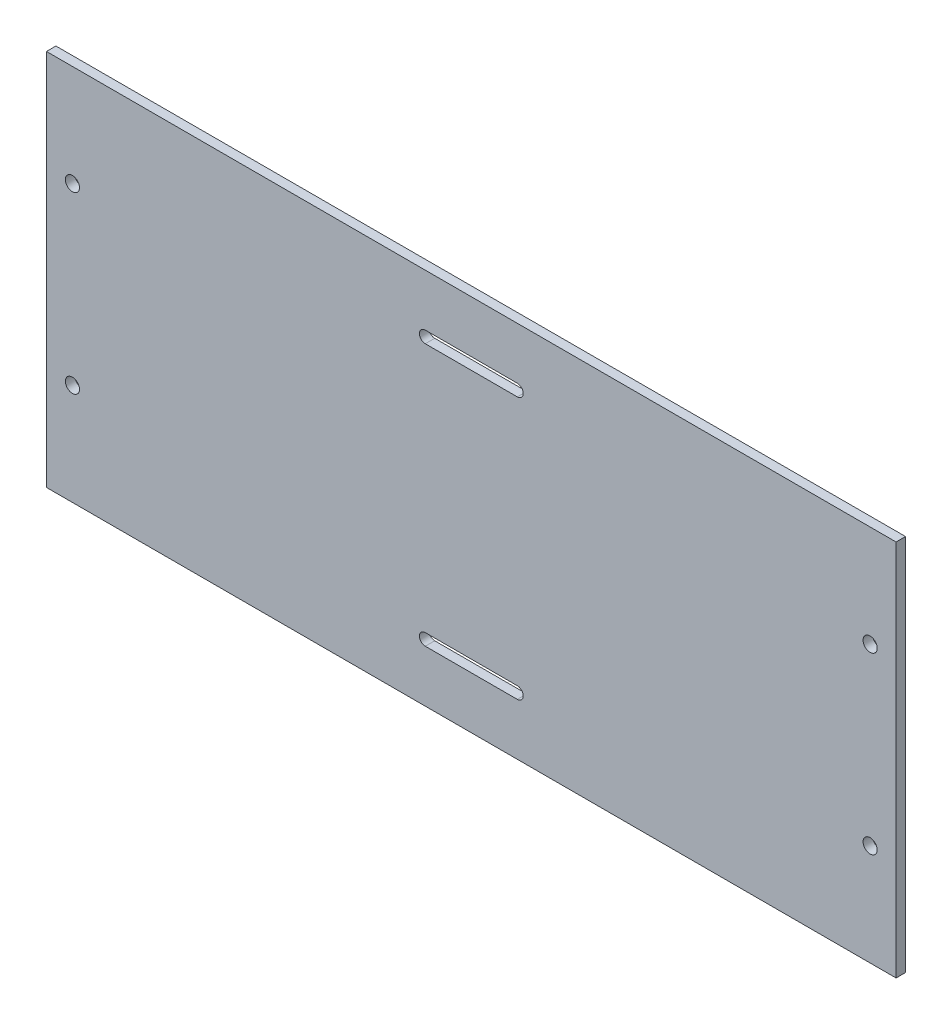
SolidWorks part; units mm, degrees
ref_plane "Plano frontal" through (0, 0, 0) normal (0, 0, 1) x (1, 0, 0)
ref_plane "Plano superior" through (0, 0, 0) normal (0, 1, 0) x (1, 0, 0)
ref_plane "Plano direito" through (0, 0, 0) normal (1, 0, 0) x (0, 0, -1)
sketch "Esboço1" plane through (0, 0, 0) normal (0, 0, 1) x (1, 0, 0)
  line L1 (0, 0) -> (180, 0)
  line L2 (0, 0) -> (0, -80)
  line L3 (0, -80) -> (180, -80)
  line L4 (180, 0) -> (180, -80)
  dimension "D1" = 80
  dimension "D2" = 180
extrude "Ressalto-extrusão1" add sketch "Esboço1" along normal blind 2
sketch "Esboço2" plane through (0, 0, 2) normal (0, 0, 1) x (1, 0, 0)
  line L0 (0, 0) -> (0, -80) construction
  line L1 (180, 0) -> (0, 0) construction
  line L2 (0, -80) -> (180, -80) construction
  line L3 (180, -80) -> (180, 0) construction
  circle A0 centre (5.5, -58.5) radius 1.5
  circle A1 centre (5.5, -21.5) radius 1.5
  circle A2 centre (174.5, -21.5) radius 1.5
  circle A3 centre (174.5, -58.5) radius 1.5
  point P14 (0, 0)
  point P15 (0, 0)
  point P16 (0, 0)
  point P19 (0, 0)
  dimension "D1" = 3
  dimension "D5" = 5.5
  dimension "D2" = 5.5
  dimension "D3" = 21.5
  dimension "D4" = 21.5
extrude "Corte-extrusão1" cut sketch "Esboço2" against normal blind 2
sketch "Esboço3" plane through (0, 0, 0) normal (0, 0, 1) x (1, 0, 0)
  line L0 (0, 0) -> (0, -80) construction
  line L1 (79, -11) -> (101, -11)
  line L2 (79, -11) -> (79, -13.5)
  line L3 (79, -13.5) -> (101, -13.5)
  line L4 (101, -11) -> (101, -13.5)
  line L5 (79, -66.5) -> (101, -66.5)
  line L6 (79, -66.5) -> (79, -69)
  line L7 (79, -69) -> (101, -69)
  line L8 (101, -66.5) -> (101, -69)
  line L9 (180, 0) -> (0, 0) construction
  line L10 (0, -80) -> (180, -80) construction
  point P8 (79, -12.25)
  point P13 (79, -67.75)
  dimension "D1" = 22
  dimension "D2" = 2.5
  dimension "D3" = 22
  dimension "D4" = 2.5
  dimension "D5" = 79
  dimension "D6" = 11
  dimension "D7" = 11
extrude "Corte-extrusão2" cut sketch "Esboço3" along normal blind 2
fillet "Filete4" 2 edges at (79, -11, 1) (79, -13.5, 1) type full round first side face at (90, -11, 1) second side face at (90, -13.5, 1) middle face at (79, -12.25, 1)
fillet "Filete5" 2 edges at (101, -11, 1) (101, -13.5, 1) type full round first side face at (90.625, -11, 1) second side face at (90.625, -13.5, 1) middle face at (101, -12.25, 1)
fillet "Filete6" 2 edges at (79, -66.5, 1) (79, -69, 1) type full round first side face at (90, -66.5, 1) second side face at (90, -69, 1) middle face at (79, -67.75, 1)
fillet "Filete7" 2 edges at (101, -66.5, 1) (101, -69, 1) type full round first side face at (90.625, -66.5, 1) second side face at (90.625, -69, 1) middle face at (101, -67.75, 1)
